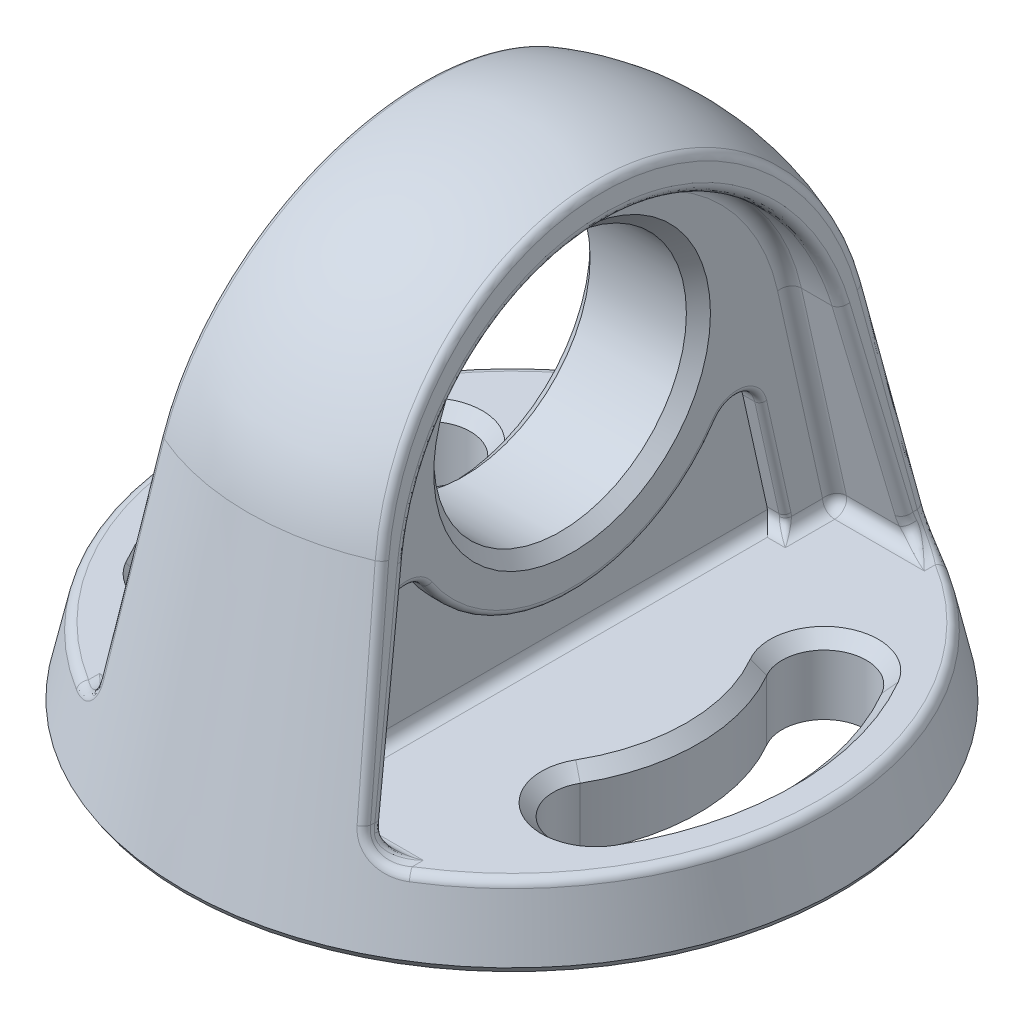
SolidWorks part; units mm, degrees
ref_plane "Front Plane" through (0, 0, 0) normal (0, 0, 1) x (1, 0, 0)
ref_plane "Top Plane" through (0, 0, 0) normal (0, 1, 0) x (1, 0, 0)
ref_plane "Right Plane" through (0, 0, 0) normal (1, 0, 0) x (0, 0, -1)
sketch "Sketch1" plane through (0, 0, 0) normal (1, 0, 0) x (0, 0, -1)
  line L0 (-55, 0) -> (0, 0)
  line L1 (0, 0) -> (0, 85)
  line L2 (-43.9259, 49.7731) -> (-55, 0)
  arc A0 (0, 85) -> (-43.9259, 49.7731) centre (0, 40) ccw
  dimension "D3" = 45
  dimension "D1" = 55
  dimension "D2" = 85
revolve "Revolve1" add sketch "Sketch1" angle 360 about L1
sketch "Sketch2" plane through (0, 0, 0) normal (0, 0, 1) x (1, 0, 0)
  line L0 (0, 0) -> (0, 85) construction
  line L1 (55, 0) -> (-55, 0)
  line L2 (-55, 0) -> (-52.3301, 12)
  line L3 (-43.9259, 49.7731) -> (-55, 0) construction
  line L4 (-52.3301, 12) -> (-22.4021, 12)
  line L5 (-22.4021, 12) -> (-15, 82.4264)
  line L6 (55, 0) -> (52.3301, 12)
  line L7 (52.3301, 12) -> (22.4021, 12)
  line L8 (22.4021, 12) -> (15, 82.4264)
  arc A0 (43.9259, 49.7731) -> (-43.9259, 49.7731) centre (0, 40) ccw construction
  point P17 (-9.3784, 84.0119)
  dimension "D1" = 30
  dimension "D2" = 12
  dimension "D3" = 12
extrude "Cut-Extrude2" cut sketch "Sketch2" against normal through all and the other way through all flip side to cut
sketch "Sketch9" plane through (0, 0, 0) normal (1, 0, 0) x (0, 0, -1)
  line L0 (-31.3633, 32.5653) -> (-35.9389, 12)
  line L1 (0, 50) -> (0, 40) construction
  line L2 (31.3633, 32.5653) -> (35.9389, 12)
  line L6 (47.2925, 12) -> (-47.2925, 12) construction
  line L7 (44.1345, 12) -> (-44.1345, 12)
  line L8 (47.1909, -1.7374) -> (36.1169, 48.0357)
  line L9 (-36.1169, 48.0357) -> (-47.1909, -1.7374)
  line L10 (44.1345, 12) -> (36.1169, 48.0357)
  line L11 (-36.1169, 48.0357) -> (-44.1345, 12)
  arc A0 (-24.1304, 33.9151) -> (24.1304, 33.9151) centre (0, 50) ccw
  arc A1 (31.3633, 32.5653) -> (24.1304, 33.9151) centre (27.4588, 31.6965) ccw
  arc A2 (-24.1304, 33.9151) -> (-31.3633, 32.5653) centre (-27.4588, 31.6965) ccw
  circle A3 centre (0, 50) radius 21
  arc A4 (36.1169, 48.0357) -> (-36.1169, 48.0357) centre (0, 40) ccw
  arc A5 (36.1169, 48.0357) -> (-36.1169, 48.0357) centre (0, 40) ccw
  point P18 (28.5793, 45.0781)
  point P21 (-28.5793, 45.0781)
  dimension "D2" = 42
  dimension "D5" = 29
  dimension "D6" = 4
  dimension "D3" = 50
  dimension "D4" = 8
  dimension "D1" = 8
extrude "Cut-Extrude3" cut sketch "Sketch9" against normal through all both and the other way through all contours A3 region at (0, 50, 0)
extrude "Cut-Extrude18" cut sketch "Sketch9<27>" against normal through all from offset 10 contours L10 A5 L11 L7 L0 A2 A0 A1 L2 A3 region at (0, 22.5207, 34.7211) offset against normal yes
sketch "Sketch9<27>" plane through (0, 0, 0) normal (1, 0, 0) x (0, 0, -1) same geometry as "Sketch9"
extrude "Cut-Extrude19" cut sketch "Sketch9<28>" along normal through all from offset 10 contours L10 A5 L11 L7 L0 A2 A0 A1 L2 A3 region at (0, 22.5207, 34.7211)
sketch "Sketch9<28>" plane through (0, 0, 0) normal (1, 0, 0) x (0, 0, -1) same geometry as "Sketch9"
extrude "Cut-Extrude21" cut sketch "Sketch9<30>" against normal through all from offset 7 contours A0 A2 L0 L7 L2 A1 region at (0, 20.3892, 0) offset against normal yes
sketch "Sketch9<30>" plane through (0, 0, 0) normal (1, 0, 0) x (0, 0, -1) same geometry as "Sketch9"
extrude "Cut-Extrude22" cut sketch "Sketch9<31>" along normal through all from offset 7 contours A0 A2 L0 L7 L2 A1 region at (0, 20.3892, 0)
sketch "Sketch9<31>" plane through (0, 0, 0) normal (1, 0, 0) x (0, 0, -1) same geometry as "Sketch9"
sketch "Sketch13" plane through (0, 12, 0) normal (0, 1, 0) x (1, 0, 0)
  line L0 (-32.909, 19) -> (0, 0) construction
  line L1 (0, 0) -> (-32.909, -19) construction
  line L2 (-38, 0) -> (0, 0) construction
  line L3 (0, 60.8241) -> (0, -60.8241) construction
  circle A0 centre (0, 0) radius 38 construction
  arc A1 (-32.909, 19) -> (-32.909, -19) centre (0, 0) ccw construction
  arc A2 (-38.9711, 22.5) -> (-38.9711, -22.5) centre (0, 0) ccw
  arc A3 (-26.8468, 15.5) -> (-26.8468, -15.5) centre (0, 0) ccw
  arc A4 (-26.8468, 15.5) -> (-38.9711, 22.5) centre (-32.909, 19) ccw
  arc A5 (-38.9711, -22.5) -> (-26.8468, -15.5) centre (-32.909, -19) ccw
  arc A6 (32.909, 19) -> (32.909, -19) centre (0, 0) cw construction
  arc A7 (38.9711, 22.5) -> (38.9711, -22.5) centre (0, 0) cw
  arc A8 (26.8468, 15.5) -> (26.8468, -15.5) centre (0, 0) cw
  arc A9 (26.8468, 15.5) -> (38.9711, 22.5) centre (32.909, 19) cw
  arc A10 (38.9711, -22.5) -> (26.8468, -15.5) centre (32.909, -19) cw
  point P5 (-38, 0)
  point P18 (0, 0)
  point P20 (38, 0)
  dimension "D1" = 76
  dimension "D2" = 7
  dimension "D3" = 60
extrude "Cut-Extrude23" cut sketch "Sketch13" against normal through all
chamfer "Chamfer2" distance 2 angle 45 10 edges at (-45, 12, 0) (-29.409, 12, -25.0622) (-31, 12, 0) (-29.409, 12, 25.0622) (-10, 50, -21) (29.409, 12, 25.0622) (45, 12, 0) (29.409, 12, -25.0622) (31, 12, 0) (10, 50, -21)
chamfer "Chamfer3" distance 1 angle 45 1 edges at (0, 0, -55) first distance on face at (0, 0, -55)
fillet "Fillet1" radius 5 4 edges at (-22.4021, 12, 45.7135) (-22.4021, 12, -45.7135) (22.4021, 12, -45.7135) (22.4021, 12, 45.7135)
fillet "Fillet2" radius 2 19 edges at (-10, 30.0178, 40.1257) (-10, 77, 0) (10, 30.0178, -40.1257) (10, 77, 0) (-18.4521, 12, 44.1345) (-8.5, 12, 35.9389) (-10, 12, 40.0367) (-7, 12, 0) (-18.4521, 12, -44.1345) (-10, 12, -40.0367) (-10, 30.0178, -40.1257) (10, 30.0178, 40.1257) (18.4521, 12, 44.1345) (10, 12, 40.0367) (8.5, 12, 35.9389) (18.4521, 12, -44.1345) (10, 12, -40.0367) (8.5, 12, -35.9389) (7, 12, 0)
fillet "Fillet3" radius 1 17 edges at (-10.5858, 12.5858, 34.8592) (-10, 14.2185, 35.433) (-10, 23.4998, 33.3803) (-10, 35.6286, 28.1926) (-10.5858, 12.5858, -35.8085) (-10, 23.2826, -33.4286) (-10, 35.6286, -28.1926) (10.5858, 12.5858, 34.8592) (10, 14.2185, 35.433) (10, 23.4998, 33.3803) (10, 35.6286, 28.1926) (10.5858, 12.5858, -34.8592) (10, 14.2185, -35.433) (10, 23.4998, -33.3803) (10, 35.6286, -28.1926) (-10, 21, 0) (10, 21, 0)
fillet "Fillet4" radius 1.5 26 edges at (24.1065, 12.8559, -43.281) (22.1608, 15.4188, -43.3738) (20.2731, 32.2565, -39.6276) (15.5703, 77, 0) (24.1065, 12.8559, 43.281) (22.1608, 15.4188, 43.3738) (23.6756, 13.1821, 46.3729) (52.3301, 12, 0) (23.0862, 13.7714, -46.5228) (-24.1065, 12.8559, -43.281) (-22.1608, 15.4188, -43.3738) (-20.2731, 32.2565, -39.6276) (-24.1065, 12.8559, 43.281) (-22.1608, 15.4188, 43.3738) (-20.2731, 32.2565, 39.6276) (-23.6756, 13.1821, -46.3729) (-52.3301, 12, 0) (-23.0862, 13.7714, 46.5228) (20.2731, 32.2565, 39.6276) (15, 82.4264, 0) (-15.5703, 77, 0) (-15, 82.4264, 0)
